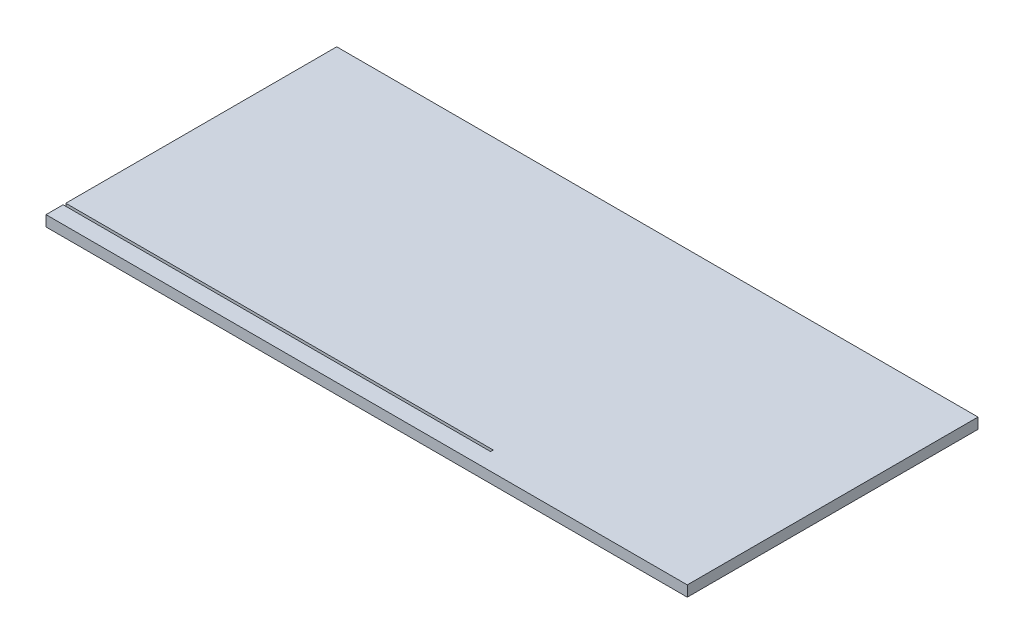
SolidWorks part; units mm, degrees
ref_plane "Front Plane" through (0, 0, 0) normal (0, 0, 1) x (1, 0, 0)
ref_plane "Top Plane" through (0, 0, 0) normal (0, 1, 0) x (1, 0, 0)
ref_plane "Right Plane" through (0, 0, 0) normal (1, 0, 0) x (0, 0, -1)
sketch "Sketch1" plane through (0, 0, 0) normal (0, 1, 0) x (1, 0, 0)
  line L1 (0, 0) -> (600, 0)
  line L2 (0, 0) -> (0, 272)
  line L3 (0, 272) -> (600, 272)
  line L4 (600, 0) -> (600, 272)
  dimension "D1" = 600
  dimension "D2" = 272
extrude "Boss-Extrude1" add sketch "Sketch1" along normal blind 10
sketch "Sketch2" plane through (0, 10, 0) normal (0, 1, 0) x (1, 0, 0)
  line L0 (0, 272) -> (0, 0) construction
  line L1 (400, 16) -> (0, 16)
  line L2 (400, 16) -> (400, 18.5)
  line L3 (400, 18.5) -> (0, 18.5)
  line L4 (0, 16) -> (0, 18.5)
  line L5 (0, 0) -> (600, 0) construction
  dimension "D1" = 16
  dimension "D2" = 2.5
  dimension "D3" = 400
extrude "Cut-Extrude1" cut sketch "Sketch2" against normal blind 2.5
